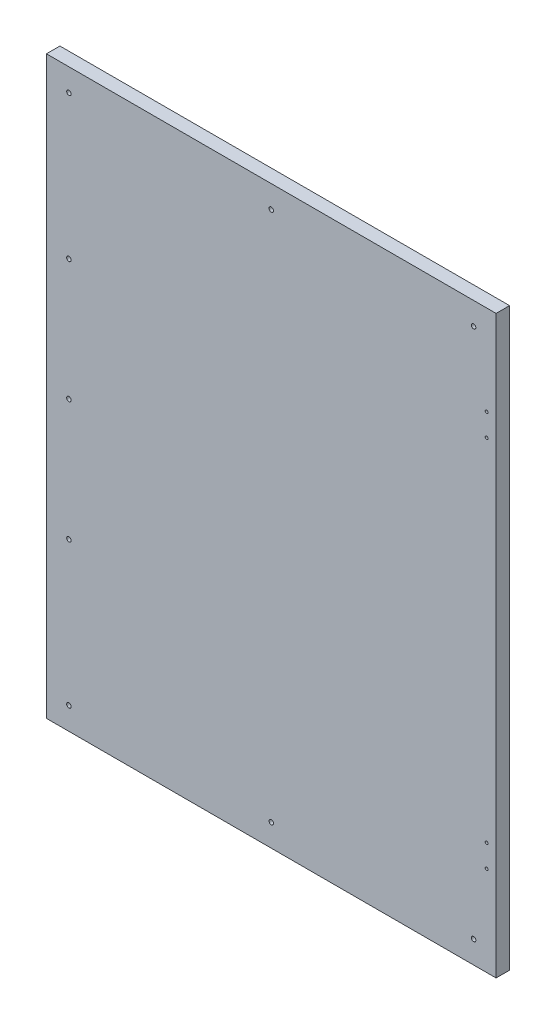
SolidWorks part; units mm, degrees
material "西洋杉"
ref_plane "正面" through (0, 0, 0) normal (0, 0, 1) x (1, 0, 0)
ref_plane "平面" through (0, 0, 0) normal (0, 1, 0) x (1, 0, 0)
ref_plane "右側面" through (0, 0, 0) normal (1, 0, 0) x (0, 0, -1)
sketch "ｽｹｯﾁ1" plane through (0, 0, 0) normal (0, 0, 1) x (1, 0, 0)
  line L1 (-250, 320) -> (250, 320)
  line L2 (-250, 320) -> (-250, -320)
  line L3 (-250, -320) -> (250, -320)
  line L4 (250, 320) -> (250, -320)
  line L5 (-250, 320) -> (250, -320) construction
  line L6 (-250, -320) -> (250, 320) construction
  point P0 (0, 0)
  dimension "D1" = 640
  dimension "D2" = 500
extrude "ﾎﾞｽ - 押し出し1" add sketch "ｽｹｯﾁ1" along normal blind 15
sketch "ｽｹｯﾁ2" plane through (0, 0, 15) normal (0, 0, 1) x (1, 0, 0)
  line L0 (-225, 295) -> (-225, -295) construction
  line L1 (-225, -295) -> (225, -295) construction
  line L2 (225, -295) -> (225, 295) construction
  line L3 (225, 295) -> (-225, 295) construction
  line L4 (-250, 320) -> (-250, -320) construction
  line L5 (250, 320) -> (-250, 320) construction
  line L6 (250, -320) -> (250, 320) construction
  line L7 (-250, -320) -> (250, -320) construction
  line L8 (-250, -320) -> (250, -320) construction
  line L9 (-250, 320) -> (-250, -320) construction
  circle A0 centre (-225, 135) radius 2.5
  circle A1 centre (-225, 0) radius 2.5
  circle A2 centre (-225, -135) radius 2.5
  circle A6 centre (0, 295) radius 2.5
  circle A7 centre (-225, 295) radius 2.5
  circle A8 centre (225, 295) radius 2.5
  circle A9 centre (125, 135) radius 2.5 [skipped]
  circle A10 centre (125, 0) radius 2.5 [skipped]
  circle A11 centre (125, -135) radius 2.5 [skipped]
  point P29 (175, 0)
  dimension "D5" = 5
  dimension "D11" = 5
  dimension "D12" = 5
  dimension "D13" = 5
  dimension "D14" = 225
  dimension "D15" = 225
  dimension "D1" = 25
  dimension "D2" = 25
  dimension "D3" = 25
  dimension "D4" = 25
  dimension "D6" = 160
  dimension "D7" = 640
  dimension "D8" = 500
  dimension "D9" = 3
  dimension "D10" = 2
extrude "ｶｯﾄ - 押し出し1" cut sketch "ｽｹｯﾁ2" against normal through all and the other way through all contours A2 | A1 | A0 region at (-225, -135, 15)
extrude "ｶｯﾄ - 押し出し2" cut sketch "ｽｹｯﾁ2<3>" against normal through all contours A7 | A6 | A8
sketch "ｽｹｯﾁ2<3>" plane through (0, 0, 15) normal (0, 0, 1) x (1, 0, 0) same geometry as "ｽｹｯﾁ2"
mirror "ﾐﾗｰ1" about plane through (0, 0, 0) normal (0, 1, 0) of "ｶｯﾄ - 押し出し2"
sketch "ｽｹｯﾁ3" plane through (0, 0, 15) normal (0, 0, 1) x (1, 0, 0)
  line L0 (239.5, 320) -> (239.5, -320) construction
  line L1 (250, 320) -> (-250, 320) construction
  line L2 (-250, -320) -> (250, -320) construction
  line L3 (250, -320) -> (250, 320) construction
  circle A0 centre (239.5, -220) radius 1.6
  circle A1 centre (239.5, -195) radius 1.6
  dimension "D2" = 3.2
  dimension "D3" = 3.2
  dimension "D4" = 25
  dimension "D5" = 100
  dimension "D1" = 10.5
extrude "ｶｯﾄ - 押し出し3" cut sketch "ｽｹｯﾁ3" against normal through all
mirror "ﾐﾗｰ2" about plane through (0, 0, 0) normal (0, 1, 0) of "ｶｯﾄ - 押し出し3"
